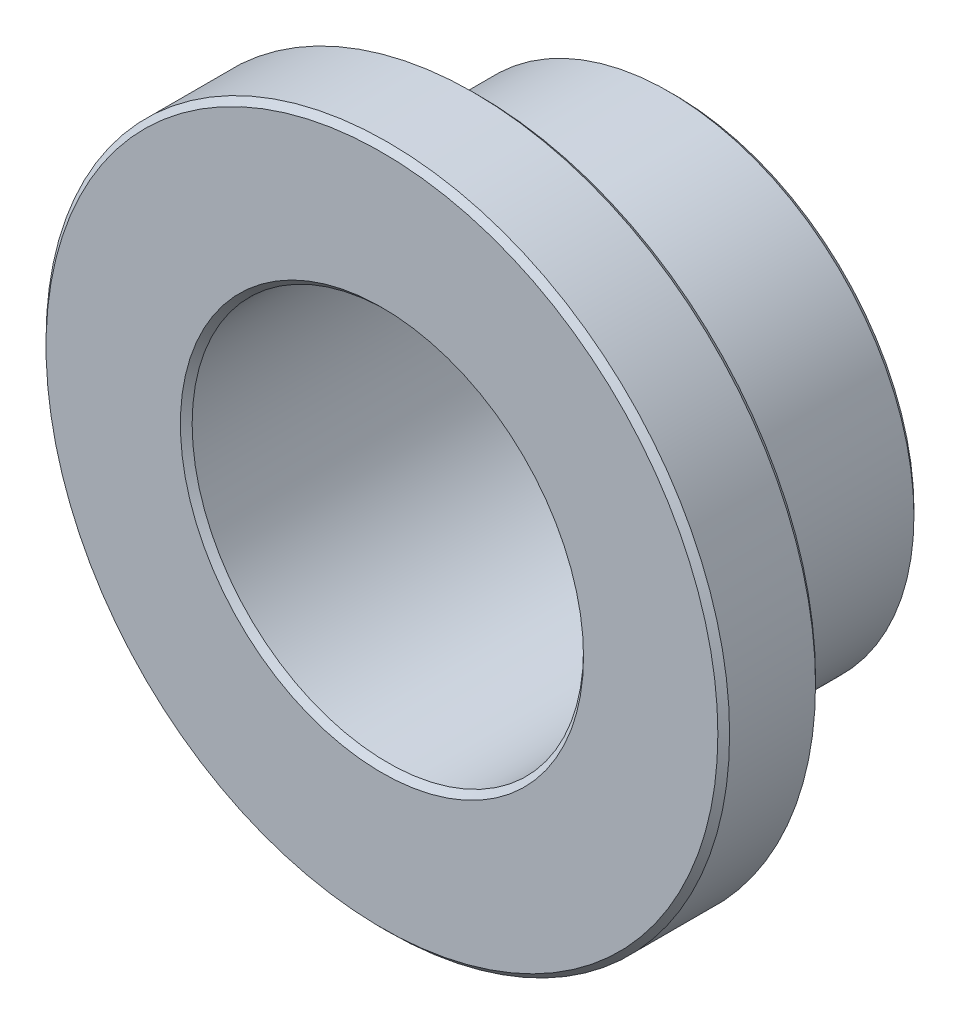
SolidWorks part; units mm, degrees
ref_plane "Front" through (0, 0, 0) normal (0, 0, 1) x (1, 0, 0)
ref_plane "Top" through (0, 0, 0) normal (0, 1, 0) x (1, 0, 0)
ref_plane "Right" through (0, 0, 0) normal (1, 0, 0) x (0, 0, -1)
sketch "Sketch1" plane through (0, 0, 0) normal (0, 0, 1) x (1, 0, 0)
  circle A0 centre (0, 0) radius 6.3627
  circle A1 centre (0, 0) radius 7.9629
  circle A2 centre (0, 0) radius 11.1125
  dimension "ID" = 12.7254
  dimension "OD" = 15.9258
  dimension "Flange OD" = 22.225
sketch "Sketch2" plane through (0, 0, 0) normal (1, 0, 0) x (0, 0, -1)
  line L0 (-4.7625, -11.1125) -> (4.7625, -11.1125) construction
  line L1 (0, 11.1125) -> (0, -11.1125) construction
  line L3 (-1.5875, 7.9629) -> (4.7625, 7.9629) construction
  point P3 (0, -11.1125)
  point P7 (0, 7.9629)
  point P9 (-1.5875, -11.1125)
  point P10 (-4.7625, 11.1125)
  point P23 (0, 11.1125)
  dimension "Flange Thickness" = 3.175
  dimension "Length" = 9.525
sketch "Sketch3" plane through (0, 0, 0) normal (0, 0, 1) x (1, 0, 0)
  circle A0 centre (0, 0) radius 11.1125 construction
  circle A1 centre (0, 0) radius 11.1125
  circle A2 centre (0, 0) radius 6.3627 construction
  circle A3 centre (0, 0) radius 6.3627
extrude "Boss-Extrude1" add sketch "Sketch3" against normal up to vertex (-1.5875 mm away) from vertex up to point (0, -11.1125, 1.5875) starting at point (0, -11.1125, 4.7625)
sketch "Sketch4" plane through (0, 0, 0) normal (0, 0, 1) x (1, 0, 0)
  circle A0 centre (0, 0) radius 6.3627 construction
  circle A1 centre (0, 0) radius 7.9629 construction
  circle A2 centre (0, 0) radius 6.3627
  circle A3 centre (0, 0) radius 7.9629
extrude "Boss-Extrude2" add sketch "Sketch4" against normal up to vertex (4.7625 mm away) from vertex up to point (0, 7.9629, -4.7625) starting at point (0, -11.1125, 1.5875)
chamfer "Chamfer1" distance 0.1909 angle 45 6 edges at (6.3627, 0, 4.7625) (11.1125, 0, 4.7625) (11.1125, 0, 1.5875) (7.9629, 0, 1.5875) (6.3627, 0, -4.7625) (7.9629, 0, -4.7625)
equation "\"D1@Chamfer1\"=\"ID@Sketch1\"*0.015"
